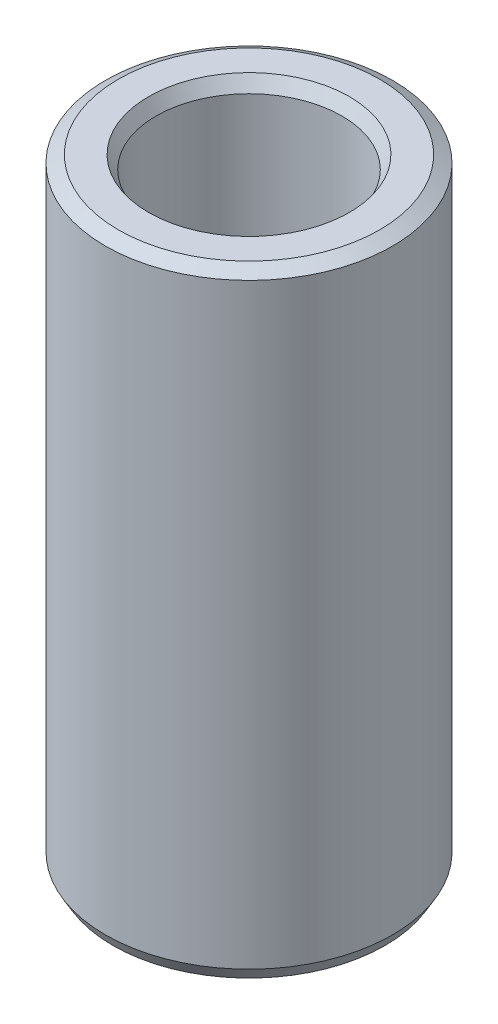
SolidWorks part; units mm, degrees
ref_plane "Front Plane" through (0, 0, 0) normal (0, 0, 1) x (1, 0, 0)
ref_plane "Top Plane" through (0, 0, 0) normal (0, 1, 0) x (1, 0, 0)
ref_plane "Right Plane" through (0, 0, 0) normal (1, 0, 0) x (0, 0, -1)
sketch "Sketch1" plane through (0, 0, 0) normal (0, 1, 0) x (1, 0, 0)
  circle A0 centre (0, 0) radius 27.5
  dimension "SLEEVE_OD" = 55
extrude "Boss-Extrude1" add sketch "Sketch1" along normal blind 118.183
sketch "Sketch2" plane through (0, 0, 0) normal (0, 1, 0) x (1, 0, 0)
  circle A0 centre (0, 0) radius 17.7901
  dimension "BORE_D" = 35.5802
extrude "Cut-Extrude1" cut sketch "Sketch2" along normal through all
chamfer "Chamfer1" distance 1.4376 angle 60 4 edges at (0, 118.183, 17.7901) (0, 0, 17.7901) (0, 0, 27.5) (0, 118.183, 27.5) first distance on face at (0, 118.183, 17.7901) first distance on face at (0, 0, 17.7901) first distance on face at (0, 118.183, 27.5)
